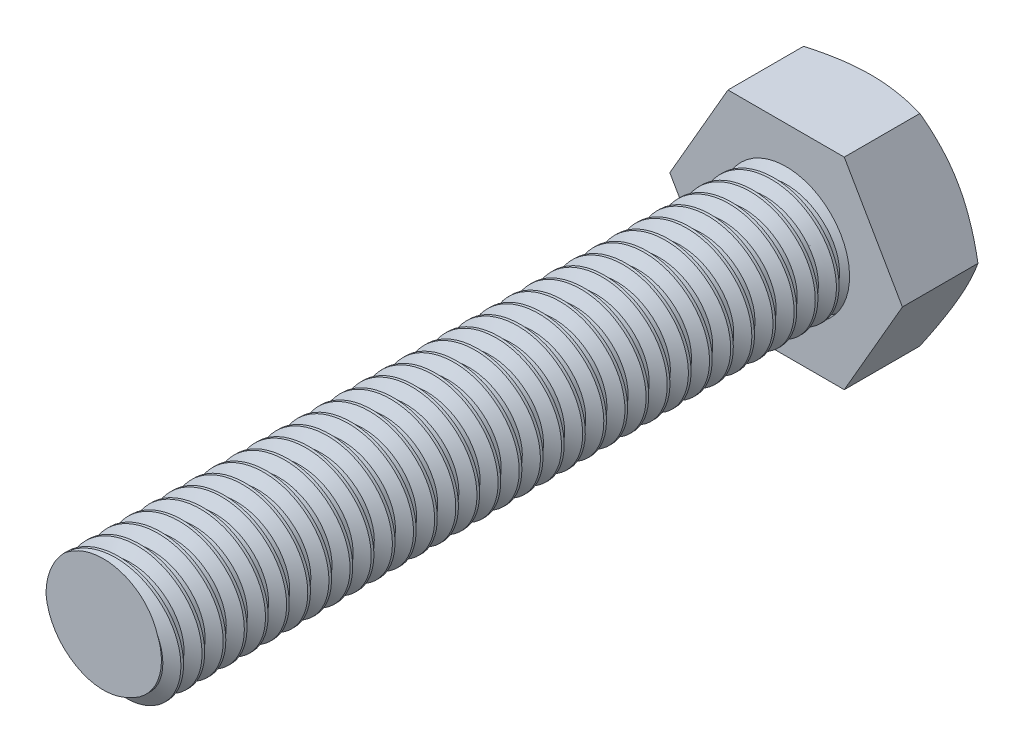
SolidWorks part; units mm, degrees
material "Alloy Steel"
ref_plane "Front Plane" through (0, 0, 0) normal (0, 0, 1) x (1, 0, 0)
ref_plane "Top Plane" through (0, 0, 0) normal (0, 1, 0) x (1, 0, 0)
ref_plane "Right Plane" through (0, 0, 0) normal (1, 0, 0) x (0, 0, -1)
sketch "Sketch1" plane through (0, 0, 0) normal (0, 0, 1) x (1, 0, 0)
  line L1 (1.375, 2.3816) -> (-1.375, 2.3816)
  line L2 (-1.375, 2.3816) -> (-2.75, 0)
  line L3 (-2.75, 0) -> (-1.375, -2.3816)
  line L4 (-1.375, -2.3816) -> (1.375, -2.3816)
  line L5 (1.375, -2.3816) -> (2.75, 0)
  line L6 (2.75, 0) -> (1.375, 2.3816)
  circle A0 centre (0, 0) radius 2.3816 construction
  dimension "D1" = 5.5
extrude "Boss-Extrude1" add sketch "Sketch1" along normal blind 1 and the other way blind 1 contours L1 L2 L3 L4 L5 L6
sketch "Sketch2" plane through (0, 0, 1) normal (0, 0, 1) x (1, 0, 0)
  circle A0 centre (0, 0) radius 1.5
extrude "Boss-Extrude2" add sketch "Sketch2" along normal blind 16
thread "Thread1" pitch 0.5 method cut profile "Thread Profile1" start angle 0, offset 1, length 0, pitch 0.5, diameter 3
ref_plane "Plane1" through (-1.5, 0, 18) normal (0, -1, 0) x (-1, 0, 0)
sketch "Thread Profile1" plane through (-1.5, 0, 18) normal (0, -1, 0) x (-1, 0, 0)
  line L0 (0, 0) -> (0, 0.5) construction
  line L11 (0, 0) -> (0, 0.4375)
  line L12 (0, 0.4375) -> (-0.2706, 0.2812)
  line L13 (-0.2706, 0.2812) -> (-0.2706, 0.1562)
  line L15 (-0.2706, 0.1562) -> (0, 0)
  line L17 (-0.2706, 0.2187) -> (0, 0.2187) construction
  point P2 (0, 0)
  dimension "Pitch" = 0.5
  dimension "Profile_Angle" = 60
  dimension "Profile_Land" = 0.125
  dimension "Profile_Height" = 0.2706
sketch "Sketch24" plane through (0, 0, -1) normal (0, 0, -1) x (-1, 0, 0)
  line L0 (1.375, -2.3816) -> (-1.375, -2.3816) construction
  circle A0 centre (0, 0) radius 2.3816
extrude "Cut-Extrude3" cut sketch "Sketch24" against normal blind 0.75 draft 60 flip side to cut contours A0
ref_axis "Axis1" through (0, 0, 15.1557) along (0, 0, -1)
